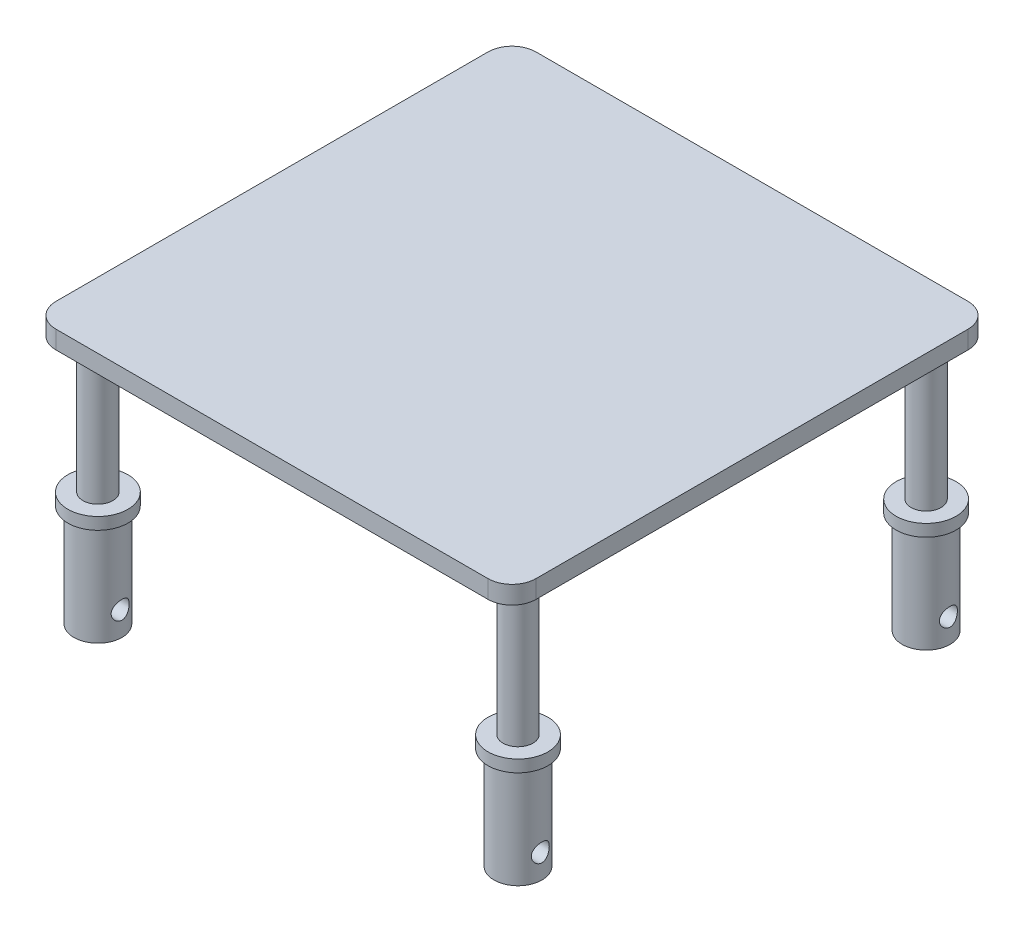
SolidWorks part; units mm, degrees
ref_plane "Front Plane" through (0, 0, 0) normal (0, 0, 1) x (1, 0, 0)
ref_plane "Top Plane" through (0, 0, 0) normal (0, 1, 0) x (1, 0, 0)
ref_plane "Right Plane" through (0, 0, 0) normal (1, 0, 0) x (0, 0, -1)
sketch "Sketch1" plane through (0, 0, 0) normal (0, 1, 0) x (1, 0, 0)
  line L1 (-36, -40) -> (36, -40)
  line L2 (-40, -36) -> (-40, 36)
  line L3 (-36, 40) -> (36, 40)
  line L4 (40, -36) -> (40, 36)
  line L5 (-40, -40) -> (40, 40) construction
  line L6 (-40, 40) -> (40, -40) construction
  circle A0 centre (-35, 34) radius 2.5
  circle A1 centre (-35, -34) radius 2.5
  circle A2 centre (35, -34) radius 2.5
  circle A3 centre (35, 34) radius 2.5
  arc A4 (-36, -40) -> (-40, -36) centre (-36, -36) cw
  arc A5 (36, -40) -> (40, -36) centre (36, -36) ccw
  arc A6 (36, 40) -> (40, 36) centre (36, 36) cw
  arc A7 (-40, 36) -> (-36, 40) centre (-36, 36) cw
  point P0 (0, 0)
  point P6 (-35, -34)
  point P7 (35, -34)
  point P8 (35, 34)
  point P9 (-35, 34)
  dimension "D7" = 5
  dimension "D8" = 5
  dimension "D9" = 5
  dimension "D10" = 5
  dimension "D11" = 4
  dimension "D1" = 80
  dimension "D2" = 80
  dimension "D3" = 70
  dimension "D4" = 5
  dimension "D5" = 68
  dimension "D6" = 6
extrude "Boss-Extrude1" add sketch "Sketch1" along normal blind 3 contours A7 L2 A4 L1 A5 L4 A6 L3 A3 A2 A1 A0 | A0 | A3 | A1 | A2 region at (0, 0, 0) region at (-35, 0, -34) region at (-35, 0, 34) region at (35, 0, 34) region at (35, 0, -34)
extrude "Boss-Extrude2" add sketch "Sketch1<3>" against normal blind 42 contours A0 | A1 | A2 | A3 region at (-35, 0, -34) region at (-35, 0, 34) region at (35, 0, 34) region at (35, 0, -34)
sketch "Sketch1<3>" plane through (0, 0, 0) normal (0, 1, 0) x (1, 0, 0) same geometry as "Sketch1"
ref_plane "Plane1" through (-37.5, 0, 0) normal (-1, 0, 0) x (0, 0, 1)
sketch "Sketch2" plane through (-37.5, 0, 0) normal (-1, 0, 0) x (0, 0, 1)
  line L0 (-36.5, -42) -> (-31.5, -42) construction
  line L1 (-36.5, -42) -> (-31.5, -42)
  line L2 (0, 0) -> (0, -48.5521) construction
  circle A0 centre (-34, -38) radius 1.5
  circle A1 centre (34, -38) radius 1.5
  point P4 (-34, -42)
  dimension "D2" = 3
  dimension "D1" = 4
extrude "Cut-Extrude1" cut sketch "Sketch2" against normal blind 147 contours A0 | A1 region at (-37.5, -38, -34) region at (-37.5, -38, 34)
sketch "Sketch3" plane through (0, 0, 0) normal (0, -1, 0) x (1, 0, 0)
  line L0 (0, 0) -> (-66.5845, 0) construction
  circle A0 centre (35, 34) radius 5
  circle A1 centre (-35, 34) radius 5
  circle A2 centre (-35, -34) radius 5
  circle A3 centre (35, -34) radius 5
  dimension "D1" = 10
  dimension "D2" = 10
extrude "Boss-Extrude3" add sketch "Sketch3" along normal blind 2 from offset 23
sketch "Sketch4" plane through (0, -25, 0) normal (0, -1, 0) x (1, 0, 0)
  line L0 (0, 0) -> (0, 64.8393) construction
  line L1 (0, 0) -> (51.9327, 0) construction
  circle A0 centre (-35, 34) radius 4
  circle A1 centre (35, 34) radius 4
  circle A2 centre (-35, -34) radius 4
  circle A3 centre (35, -34) radius 4
  dimension "D1" = 8
extrude "Boss-Extrude4" add sketch "Sketch4" along normal up to surface (17 mm away) up to face at (35, -42, -31.5)
extrude "Cut-Extrude2" cut sketch "Sketch2<3>" against normal blind 130 and the other way blind 101 contours A0 | A1 region at (-37.5, -38, -34) region at (-37.5, -38, 34)
sketch "Sketch2<3>" plane through (-37.5, 0, 0) normal (-1, 0, 0) x (0, 0, 1) same geometry as "Sketch2"
